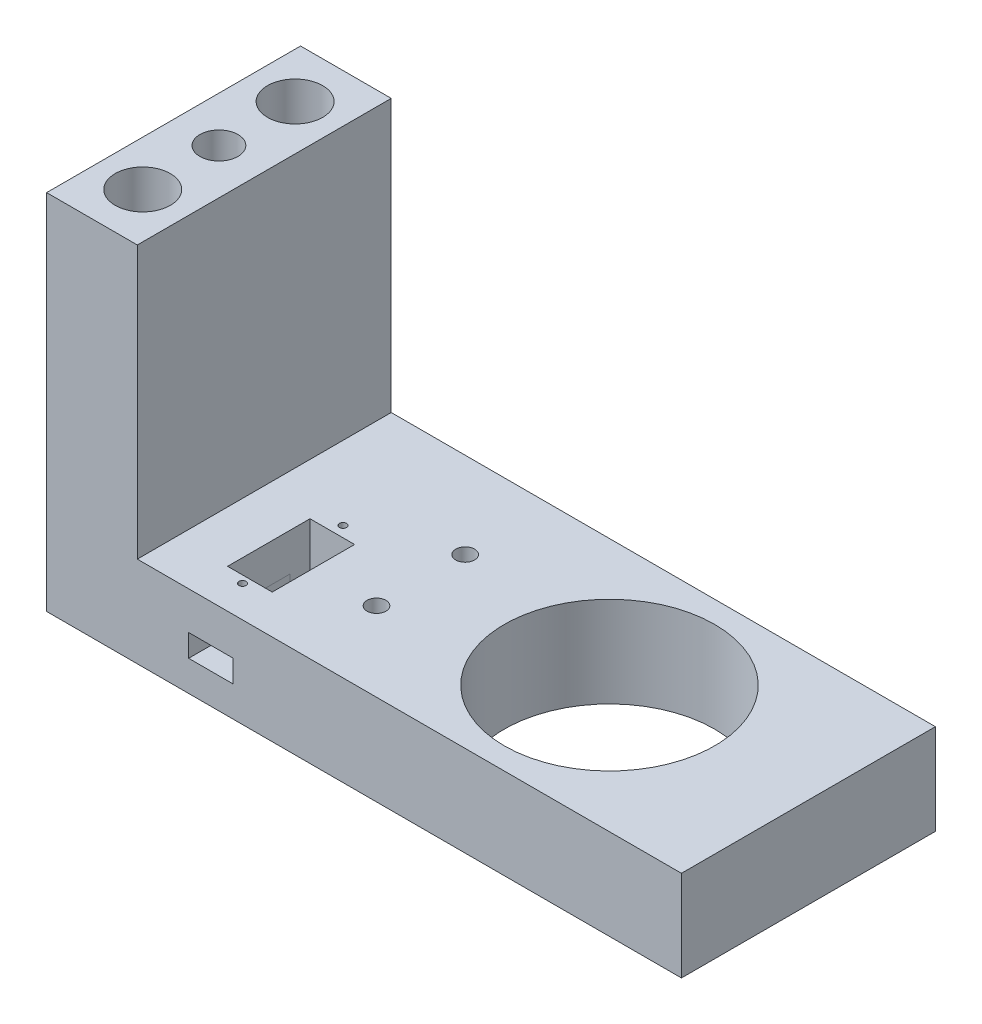
SolidWorks part; units mm, degrees
other "Markup1"
sketch "Sketch3" plane through (-12.5, 0, 35) normal (-0.5772, -0.5774, 0.5775) x (0.4082, -0.8165, -0.4082)
ref_plane "Front Plane" through (0, 0, 0) normal (0, 0, 1) x (1, 0, 0)
ref_plane "Top Plane" through (0, 0, 0) normal (0, 1, 0) x (1, 0, 0)
ref_plane "Right Plane" through (0, 0, 0) normal (1, 0, 0) x (0, 0, -1)
sketch "Sketch1" plane through (0, 0, 0) normal (0, 1, 0) x (1, 0, 0)
  line L0 (12.5, 35) -> (-12.5, 35)
  line L6 (12.5, -35) -> (-12.5, -35)
  line L7 (-12.5, 35) -> (-12.5, -35)
  line L8 (12.5, 35) -> (12.5, -35)
  line L9 (0, 0) -> (0, 8.1937) construction
  circle A1 centre (0, 0) radius 11.15
  circle A2 centre (0, 21) radius 7.6
  circle A3 centre (0, -21) radius 7.6
  circle A9 centre (0, 0) radius 5.25
  circle A10 centre (0, 8.1937) radius 1.575
  circle A11 centre (8.1937, 0) radius 1.575
  circle A12 centre (0, -8.1937) radius 1.575
  circle A13 centre (-8.1937, 0) radius 1.575
  point P24 (0, 0)
  point P30 (-12.5, 0)
  point P31 (0, 35)
  point P32 (12.5, 0)
  point P33 (0, -35)
  dimension "D3" = 3.15
  dimension "D1" = 22.3
  dimension "D2" = 10.5
  dimension "D4" = 8.1937
  dimension "D10" = 15.2
  dimension "D11" = 15.2
  dimension "D7" = 4
  dimension "D5" = 25
  dimension "D6" = 70
  dimension "D8" = 21
  dimension "D9" = 21
extrude "Boss-Extrude2" add sketch "Sketch1" along normal blind 100 contours L8 L0 L7 L6 A3 A2 A1 | A1 A13 A12 A11 A9 A10 | A10 | A11 | A12 | A13 region at (11.7567, 0, 0) region at (-10.8346, 0, 0) region at (0, 0, -8.1937) region at (8.1937, 0, 0) region at (0, 0, 8.1937) region at (-8.1937, 0, 0)
extrude "Cut-Extrude5" cut sketch "Sketch1<12>" along normal blind 12.8 contours A12 | A10 | A13 | A11 region at (0, 0, -8.1937) region at (8.1937, 0, 0) region at (0, 0, 8.1937) region at (-8.1937, 0, 0)
sketch "Sketch1<12>" plane through (0, 0, 0) normal (0, 1, 0) x (1, 0, 0) same geometry as "Sketch1"
extrude "Cortar-Extruir1" cut sketch "Sketch1<27>" along normal blind 3.5 contours A1 A13 A12 A11 A9 A10 region at (-10.8346, 0, 0)
sketch "Sketch1<27>" plane through (0, 0, 0) normal (0, 1, 0) x (1, 0, 0) same geometry as "Sketch1"
sketch "Croquis1" plane through (12.5, 0, 0) normal (1, 0, 0) x (0, 0, -1)
  line L0 (35, 100) -> (35, 0) construction
  line L1 (-35, 0) -> (35, 0)
  line L2 (-35, 0) -> (-35, 25)
  line L3 (-35, 25) -> (35, 25)
  line L4 (35, 0) -> (35, 25)
  dimension "D1" = 25
extrude "Saliente-Extruir1" add sketch "Croquis1" along normal blind 150
sketch "Croquis4" plane through (0, 0, 0) normal (0, -1, 0) x (1, 0, 0)
  line L0 (38.9573, 12.9126) -> (26.6573, 12.9126) construction
  line L5 (38.9573, 1.5536) -> (26.6573, 1.5536)
  line L6 (162.5, 35) -> (-12.5, 35) construction
  line L7 (38.9573, 1.5536) -> (38.9573, 24.2716)
  line L8 (38.9573, 24.2716) -> (26.6573, 24.2716)
  line L9 (26.6573, 1.5536) -> (26.6573, 24.2716)
  line L10 (162.5, -35) -> (12.5, -35)
  line L11 (162.5, -35) -> (162.5, 35)
  line L12 (162.5, 35) -> (12.5, 35)
  line L13 (12.5, -35) -> (12.5, 35)
  circle A0 centre (107.66, 0) radius 29
  circle A1 centre (32.8073, 18.0227) radius 2.5
  circle A3 centre (32.8073, -1.3984) radius 1
  circle A4 centre (32.8073, 26.3016) radius 1
  point P4 (32.8073, 12.9126)
  dimension "D2" = 35
  dimension "D6" = 54.84
  dimension "D3" = 58
  dimension "D10" = 2
  dimension "D11" = 5
  dimension "D12" = 2
  dimension "D1" = 150
  dimension "D4" = 14.1573
  dimension "D5" = 68.7027
  dimension "D7" = 22.718
  dimension "D8" = 36.5536
  dimension "D9" = 8.2789
  dimension "D13" = 19.4211
  dimension "D14" = 8.6984
extrude "Cortar-Extruir2" cut sketch "Croquis4" against normal blind 30 contours A0 region at (107.66, 0, 0)
extrude "Cut-Extrude6" cut sketch "Croquis4<3>" along normal blind 22 from surface contours L0 L7 L8 L9 A1 | L7 L0 L9 L5 | A1 region at (32.8073, 0, 7.2331) region at (32.8073, 0, 13.08) region at (32.8073, 0, 18.0227) starting at face at (107.66, 25, -29)
sketch "Croquis4<3>" plane through (0, 0, 0) normal (0, -1, 0) x (1, 0, 0) same geometry as "Croquis4"
extrude "Cut-Extrude7" cut sketch "Croquis4<4>" along normal blind 6 from surface contours A3 | A4 region at (32.8073, 0, -1.3984) region at (32.8073, 0, 26.3016) starting at face at (87.5, 25, 0)
sketch "Croquis4<4>" plane through (0, 0, 0) normal (0, -1, 0) x (1, 0, 0) same geometry as "Croquis4"
sketch "Sketch2" plane through (0, 0, 35) normal (0, 0, 1) x (1, 0, 0)
  line L3 (38.85, 14.56) -> (38.85, 8.4)
  line L8 (38.85, 8.4) -> (26.65, 8.4)
  line L9 (26.65, 14.56) -> (26.65, 8.4)
  line L10 (38.85, 14.56) -> (26.65, 14.56)
extrude "Cut-Extrude11" cut sketch "Sketch2" against normal blind 28 from surface contours L3 L10 L9 L8 region at (32.75, 11.48, 35) starting at face at (54.1667, 41.6667, 35)
sketch "Croquis5" plane through (0, 25, 0) normal (0, 1, 0) x (1, 0, 0)
  circle A0 centre (56.6002, -13.1692) radius 2.6
  circle A1 centre (56.6002, 11.2772) radius 2.6
  dimension "D1" = 5.2
  dimension "D2" = 5.2
extrude "Cortar-Extruir3" cut sketch "Croquis5" against normal blind 50 from surface starting at face at (32.8073, 25, -2.3984)
